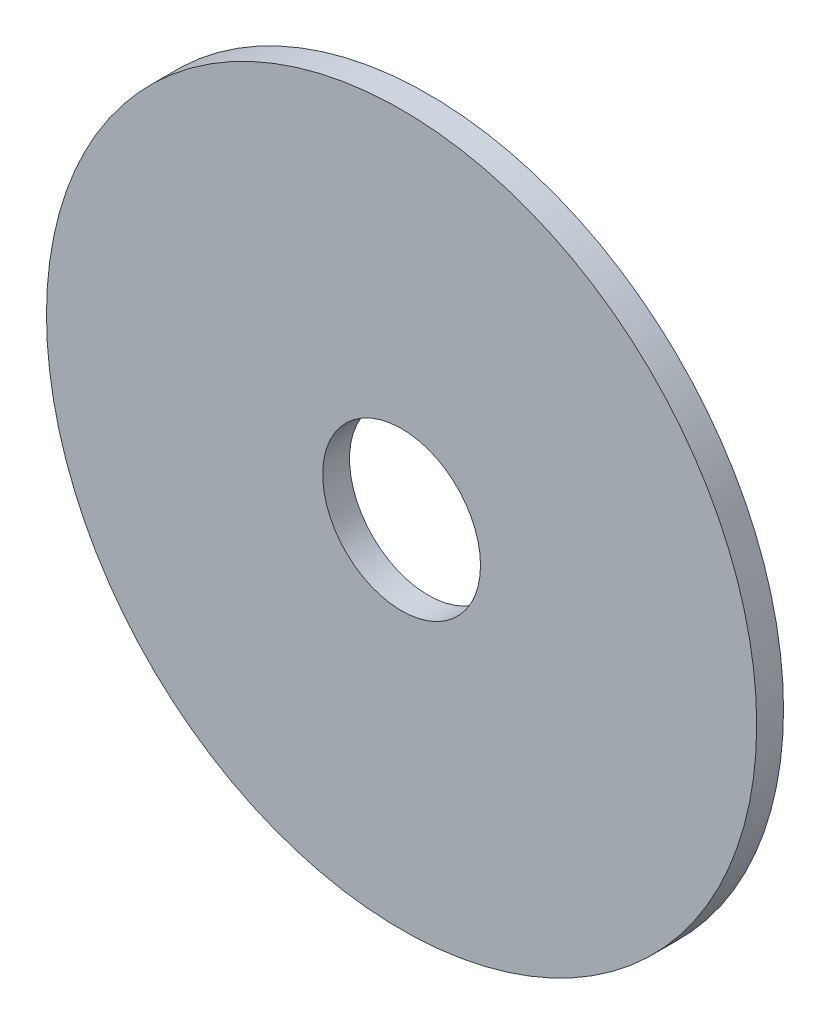
SolidWorks part; units mm, degrees
material "ABS PC"
ref_plane "Front Plane" through (0, 0, 0) normal (0, 0, 1) x (1, 0, 0)
ref_plane "Top Plane" through (0, 0, 0) normal (0, 1, 0) x (1, 0, 0)
ref_plane "Right Plane" through (0, 0, 0) normal (1, 0, 0) x (0, 0, -1)
sketch "Sketch1" plane through (0, 0, 0) normal (0, 0, 1) x (1, 0, 0)
  circle A0 centre (0, 0) radius 22.5
  circle A1 centre (0, 0) radius 5
  dimension "D1" = 45
  dimension "D2" = 10
extrude "Boss-Extrude1" add sketch "Sketch1" along normal blind 1.7
equation "\"smallPulleyTeeth\"= 15"
equation "\"largePulleyTeeth\"= 40"
equation "\"eighthThick\"= 2.9mm"
equation "\"sixteenthThick\" = 1.7mm"
equation "\"wheelEighthThick\"=3.0mm"
equation "\"quarterThick\"=5.9mm"
equation "\"bushingDiam\"= 7.85mm"
equation "\"plateBoltCircle\"= 65mm"
equation "\"plateBoltDiam\"= 5mm"
equation "\"D1@Boss-Extrude1\"=\"sixteenthThick\""
